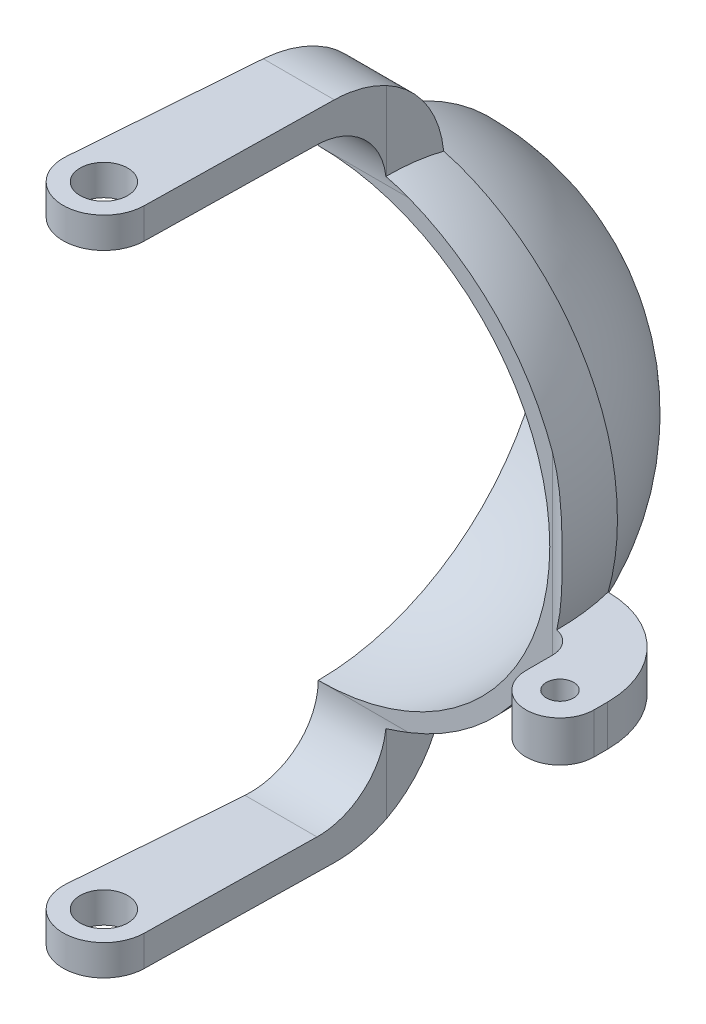
SolidWorks part; units mm, degrees
ref_plane "前视基准面" through (0, 0, 0) normal (0, 0, 1) x (1, 0, 0)
ref_plane "上视基准面" through (0, 0, 0) normal (0, 1, 0) x (1, 0, 0)
ref_plane "右视基准面" through (0, 0, 0) normal (1, 0, 0) x (0, 0, -1)
other "Configuration Table"
sketch "草图1" plane through (0, 0, 0) normal (1, 0, 0) x (0, 0, -1)
  line L0 (0, 17.75) -> (0, 17)
  line L1 (0, -17) -> (0, -17.75)
  arc A0 (0, -17.75) -> (0, 17.75) centre (0, 0) ccw
  arc A1 (0, -17) -> (0, 17) centre (0, 0) ccw
  dimension "D1" = 35.5
  dimension "D2" = 34
revolve "旋转1" add sketch "草图1" angle 90 about L0
sketch "草图2" plane through (0, 0, 0) normal (1, 0, 0) x (0, 0, -1)
  line L2 (4.25, 17.7482) -> (4.25, 17.2337)
  line L3 (0, 18.25) -> (0, 17.75)
  line L6 (0, 0) -> (23.4036, 0) construction
  arc A3 (4.25, 17.7482) -> (0, 18.25) centre (0, 0) ccw
  arc A7 (4.25, 17.2337) -> (0, 17.75) centre (0, 0) ccw
  dimension "D1" = 36.5
  dimension "D2" = 17.75
  dimension "D3" = 4.25
revolve "旋转2" add sketch "草图2" angle 180 about L6
sketch "草图3" plane through (0, 0, 0) normal (0, 1, 0) x (1, 0, 0)
  line L0 (17.7482, 4.25) -> (0, 4.25) construction
  line L1 (0, 0) -> (5, 0)
  line L2 (0, 0) -> (0, 4.25)
  line L3 (0, 4.25) -> (5, 4.25)
  line L4 (5, 0) -> (5, 4.25)
  dimension "D1" = 5
extrude "凸台-拉伸1" add sketch "草图3" against normal up to surface (6 mm away) from offset 24.25 up to face at (8.9996, 0, -2.1324)
sketch "草图4" plane through (0, 24.25, 0) normal (0, 1, 0) x (1, 0, 0)
  line L0 (-1.3035, -17.1916) -> (0, 0)
  line L1 (4.6874, -17.4721) -> (5, 0)
  line L2 (0, 0) -> (5, 0)
  circle A0 centre (1.6879, -17.4184) radius 1.75
  arc A1 (-1.3035, -17.1916) -> (4.6874, -17.4721) centre (1.6879, -17.4184) ccw
  dimension "D1" = 17.5
  dimension "D2" = 3.5
  dimension "D3" = 6
extrude "凸台-拉伸2" add sketch "草图4" against normal blind 2.25
fillet "圆角2" radius 5 1 edges at (2.5, 22, 0)
fillet "圆角3" radius 8 1 edges at (2.5, 24.25, -4.25)
mirror "镜向2" about plane through (0, 0, 0) normal (0, 1, 0) of "凸台-拉伸1", "凸台-拉伸2", "圆角2", "圆角3"
ref_plane "基准面1" through (19, 0, 0) normal (1, 0, 0) x (0, 0, -1)
sketch "草图5" plane through (19, 0, 0) normal (1, 0, 0) x (0, 0, -1)
  line L0 (0, 17) -> (0, -17) construction
  line L1 (0, -5) -> (4.25, -5)
  line L2 (0, -5) -> (0, -8)
  line L3 (0, -8) -> (4.25, -8)
  line L4 (4.25, -5) -> (4.25, -8)
  line L5 (4.25, -16.25) -> (4.25, 16.25) construction
  dimension "D1" = 5
  dimension "D2" = 3
extrude "凸台-拉伸3" add sketch "草图5" against normal up to surface (1.9706 mm away) up to face at (7.9772, -0.0237, -1.6892)
sketch "草图6" plane through (0, -8, 0) normal (0, -1, 0) x (1, 0, 0)
  line L0 (19, 0) -> (19, 3.75)
  line L2 (24, 3.75) -> (24, -4.25)
  line L3 (19, -4.25) -> (24, -4.25)
  line L4 (19, 0) -> (19, -4.25)
  arc A0 (19, 3.75) -> (24, 3.75) centre (21.5, 3.75) cw
  circle A1 centre (21.5, 3.75) radius 1
  dimension "D1" = 2
  dimension "D2" = 2.5
  dimension "D3" = 8
extrude "凸台-拉伸4" add sketch "草图6" against normal blind 3
fillet "圆角4" radius 7 1 edges at (24, -6.5, -4.25)
fillet "圆角5" radius 1.8 1 edges at (19, -6.5, 0)
